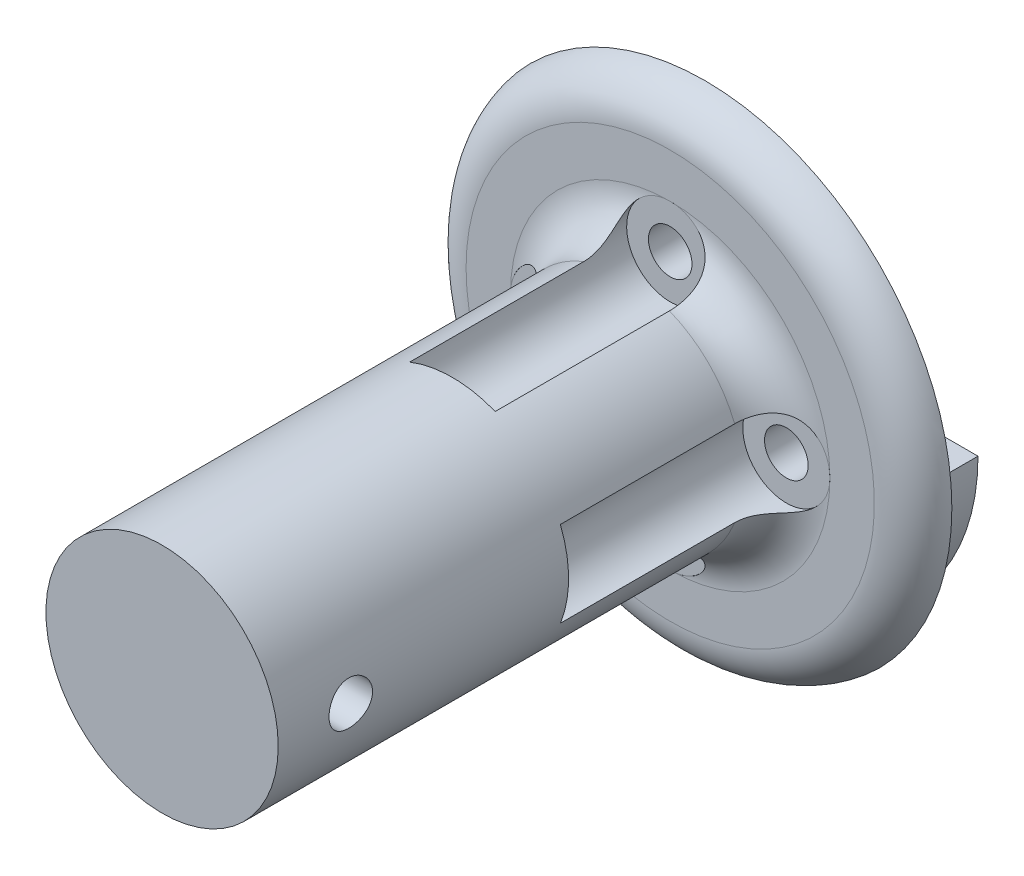
SolidWorks part; units mm, degrees
ref_plane "前视基准面" through (0, 0, 0) normal (0, 0, 1) x (1, 0, 0)
ref_plane "上视基准面" through (0, 0, 0) normal (0, 1, 0) x (1, 0, 0)
ref_plane "右视基准面" through (0, 0, 0) normal (1, 0, 0) x (0, 0, -1)
sketch "草图2" plane through (0, 0, 0) normal (0, 0, 1) x (1, 0, 0)
  line L0 (0, -14.8) -> (0, 0)
  line L1 (0, 0) -> (14.8, 0)
  arc A0 (14.8, 0) -> (0, -14.8) centre (0, 0) cw
extrude "凸台-拉伸1" add sketch "草图2" along normal blind 4
sketch "草图5" plane through (0, 0, 4) normal (0, 0, 1) x (1, 0, 0)
  circle A0 centre (0, 0) radius 17
extrude "凸台-拉伸2" add sketch "草图5" along normal blind 2.4
sketch "草图6" plane through (0, 0, 6.4) normal (0, 0, 1) x (1, 0, 0)
  circle A0 centre (0, 0) radius 9.8
extrude "凸台-拉伸3" add sketch "草图6" against normal blind 6.4
sketch "草图8" plane through (0, 0, 6.4) normal (0, 0, 1) x (1, 0, 0)
  circle A0 centre (0, 0) radius 8
extrude "凸台-拉伸5" add sketch "草图8" along normal blind 35
sketch "草图21" plane through (0, 0, 0) normal (-1, 0, 0) x (0, 0, 1)
  line L0 (41.4, -8) -> (41.4, 8) construction
  circle A0 centre (36.4, 0) radius 1.5
  dimension "D1" = 5
extrude "切除-拉伸2" cut sketch "草图21" against normal up to next and the other way up to next
fillet "圆角2" radius 3 1 edges at (-17, 0, 6.4)
sketch "草图22" plane through (0, 0, 0) normal (0, 0, -1) x (-1, 0, 0)
  line L0 (0, -9.8) -> (0, 9.8) construction
  line L2 (-9.8, 0) -> (9.8, 0) construction
  arc A0 (0, -9.8) -> (-9.8, 0) centre (0, 0) ccw construction
  circle A1 centre (0, -8) radius 1.5
  circle A2 centre (0, 8) radius 1.5
  circle A3 centre (-8, 0) radius 1.5
  circle A4 centre (8, 0) radius 1.5
  dimension "D2" = 3
  dimension "D3" = 8
  dimension "D1" = 8
extrude "切除-拉伸6" cut sketch "草图22" against normal blind 7
sketch "草图23" plane through (0, 0, 6.4) normal (0, 0, 1) x (1, 0, 0)
  line L0 (0, -14.0606) -> (0, 14.0606) construction
  line L2 (-14.0606, 0) -> (14.0606, 0) construction
  circle A0 centre (8, 0) radius 3
  circle A1 centre (0, 0) radius 14.0606 construction
  circle A2 centre (-8, 0) radius 3
  circle A3 centre (0, -8) radius 3
  circle A4 centre (0, 8) radius 3
extrude "切除-拉伸7" cut sketch "草图23" along normal blind 15
fillet "圆角3" radius 3 4 edges at (-5.6569, 5.6569, 6.4) (-5.6569, -5.6569, 6.4) (5.6569, 5.6569, 6.4) (5.6569, -5.6569, 6.4)
